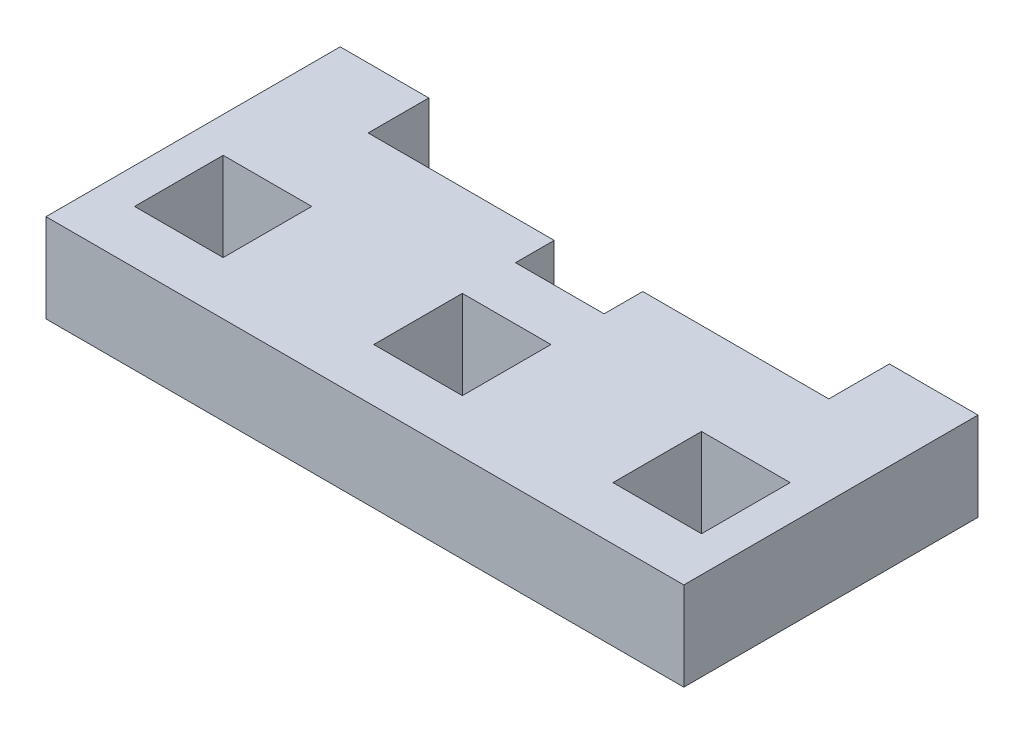
SolidWorks part; units mm, degrees
ref_plane "Front Plane" through (0, 0, 0) normal (0, 0, 1) x (1, 0, 0)
ref_plane "Top Plane" through (0, 0, 0) normal (0, 1, 0) x (1, 0, 0)
ref_plane "Right Plane" through (0, 0, 0) normal (1, 0, 0) x (0, 0, -1)
sketch "Sketch1" plane through (0, 0, 0) normal (0, 1, 0) x (1, 0, 0)
  line L0 (-22.86, 0) -> (22.86, 0) construction
  line L1 (-22.86, -6.985) -> (22.86, -6.985)
  line L2 (-22.86, -6.985) -> (-22.86, 9.7575)
  line L3 (-16.51, 9.7575) -> (-3.175, 9.7575)
  line L4 (22.86, -6.985) -> (22.86, 9.7575)
  line L5 (0, 6.985) -> (0, -6.985) construction
  line L6 (-3.175, 9.7575) -> (-3.175, 6.985)
  line L7 (-3.175, 6.985) -> (3.175, 6.985)
  line L8 (3.175, 6.985) -> (3.175, 9.7575)
  line L9 (3.175, 9.7575) -> (16.51, 9.7575)
  line L10 (-20.32, 3.175) -> (-13.97, -3.175) construction
  line L11 (-3.175, 3.175) -> (3.175, 3.175)
  line L12 (-3.175, 3.175) -> (-3.175, -3.175)
  line L13 (-3.175, -3.175) -> (3.175, -3.175)
  line L15 (22.86, 9.7575) -> (22.86, 14.1025)
  line L16 (3.175, 3.175) -> (3.175, -3.175)
  line L17 (-3.175, 3.175) -> (3.175, -3.175) construction
  line L18 (-3.175, -3.175) -> (3.175, 3.175) construction
  line L19 (-13.97, 3.175) -> (-20.32, -3.175) construction
  line L20 (13.97, 3.175) -> (20.32, -3.175) construction
  line L21 (13.97, -3.175) -> (20.32, 3.175) construction
  line L22 (20.32, -3.175) -> (13.97, -3.175)
  line L23 (20.32, -3.175) -> (20.32, 3.175)
  line L24 (20.32, 3.175) -> (13.97, 3.175)
  line L25 (13.97, -3.175) -> (13.97, 3.175)
  line L26 (22.86, 14.1025) -> (16.51, 14.1025)
  line L27 (16.51, 14.1025) -> (16.51, 9.7575)
  line L28 (-16.51, 14.1025) -> (-16.51, 9.7575)
  line L29 (-22.86, 14.1025) -> (-16.51, 14.1025)
  line L30 (-13.97, -3.175) -> (-13.97, 3.175)
  line L31 (-20.32, 3.175) -> (-13.97, 3.175)
  line L32 (-20.32, -3.175) -> (-20.32, 3.175)
  line L33 (-20.32, -3.175) -> (-13.97, -3.175)
  line L34 (-22.86, 9.7575) -> (-22.86, 14.1025)
  point P8 (0, 0)
  point P12 (0, 6.985)
  point P16 (0, 0)
  point P22 (-17.145, 0)
  point P23 (17.145, 0)
  dimension "D1" = 45.72
  dimension "D2" = 3.81
  dimension "D3" = 6.35
  dimension "D4" = 3.81
  dimension "D5" = 13.97
  dimension "D6" = 6.35
  dimension "D7" = 2.54
  dimension "D8" = 10.795
  dimension "D9" = 2.7725
  dimension "D10" = 4.345
  dimension "D11" = 6.35
extrude "Boss-Extrude1" add sketch "Sketch1" along normal blind 6.35
equation "\"Ball Diameter\"= 1.75in"
equation "\"Sheet Thickness\"= 0.25in"
equation "\"Screw Diameter\"= .17in"
equation "\"Robot Diameter\"= 14in"
equation "\"Castor Screw Diameter\"= 0.22in"
equation "\"Wheel Diameter\" = 4in"
equation "\"Nut Diameter\" = 8.4mm"
equation "\"Nut Height\" = 2.9mm"
equation "\"Screw Height\" = 0.55in"
equation "\"Pulley Diameter\" = 1in"
equation "\"Reactor Height\" = 14in"
equation "\"Elevator Height\" = 11.5in"
equation "\"Elevator Width\" = \"Ball Diameter\" + 0.25in"
equation "\"Elevator Bearing Diameter\" = sqr(2*(\"Sheet Thickness\"^2)) + 0.2in"
equation "\"Elevator Axle Endcap Diameter\" = \"Pulley Diameter\" + 0.25in"
equation "\"Elevator Axle Length\" = \"Elevator Width\" + 8*\"Sheet Thickness\""
equation "\"Elevator Clearance from Axis\" = 3.28in"
equation "\"D1@Sketch1\"=\"Elevator Width\"-0.2in"
equation "\"D3@Sketch1\" = \"Sheet Thickness\""
equation "\"D6@Sketch1\"=\"Sheet Thickness\""
equation "\"D9@Sketch1\"=(0.3in - ((\"Elevator Axle Endcap Diameter\"-\"Pulley Diameter\")/2 - 1.1mm))/2"
equation "\"D10@Sketch1\"=(\"Elevator Axle Endcap Diameter\"-\"Pulley Diameter\")/2 - 1.1mm + 2.27mm"
equation "\"D1@Boss-Extrude1\"=\"Sheet Thickness\""
equation "\"Ball Radius\" = \"Ball Diameter\"/2"
equation "\"Claw Horizontal Seperation\" = (\"Elevator Width\"/2) - (1.5 * \"Sheet Thickness\") - 0.15in"
